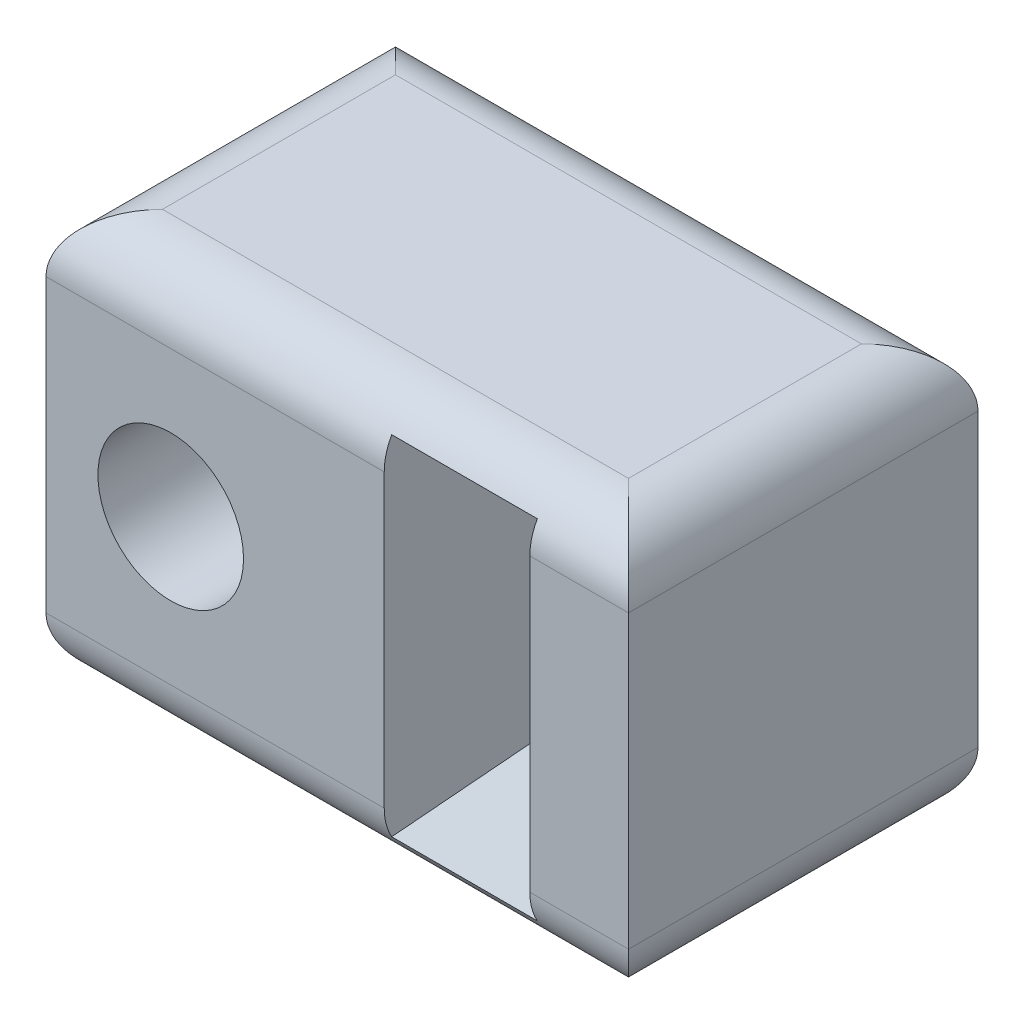
SolidWorks part; units mm, degrees
ref_plane "Front Plane" through (0, 0, 0) normal (0, 0, 1) x (1, 0, 0)
ref_plane "Top Plane" through (0, 0, 0) normal (0, 1, 0) x (1, 0, 0)
ref_plane "Right Plane" through (0, 0, 0) normal (1, 0, 0) x (0, 0, -1)
sketch "Sketch1" plane through (0, 0, 0) normal (0, 0, 1) x (1, 0, 0)
  line L0 (0, 1.9206) -> (0, -2.1822) construction
  line L2 (-5, -3.5) -> (5, -3.5)
  line L3 (-5, -3.5) -> (-5, 3.5)
  line L4 (-5, 3.5) -> (5, 3.5)
  line L5 (5, -3.5) -> (5, 3.5)
  line L6 (-5, -3.5) -> (5, 3.5) construction
  line L7 (-5, 3.5) -> (5, -3.5) construction
  point P3 (0, 0)
  dimension "D1" = 10
  dimension "D2" = 7
extrude "Boss-Extrude1" add sketch "Sketch1" along normal blind 6 contours L4 L5 L2 L3
sketch "Sketch2" plane through (0, 0, 6) normal (0, 0, 1) x (1, 0, 0)
  line L1 (0.8066, -3) -> (3.3066, -3)
  line L2 (0.8066, -3) -> (0.8066, 3)
  line L3 (0.8066, 3) -> (3.3066, 3)
  line L4 (3.3066, -3) -> (3.3066, 3)
  line L5 (0.8066, -3) -> (3.3066, 3) construction
  line L6 (0.8066, 3) -> (3.3066, -3) construction
  point P0 (2.0566, 0)
  dimension "D1" = 2.5
  dimension "D2" = 6
sketch "Sketch3" plane through (0, 0, 0) normal (0, 0, -1) x (-1, 0, 0)
  line L0 (-3.3066, -3) -> (-3.3066, 3) construction
  line L1 (-3.3066, -2.5) -> (-0.8066, -2.5)
  line L2 (-3.3066, -2.5) -> (-3.3066, 2.5)
  line L3 (-3.3066, 2.5) -> (-0.8066, 2.5)
  line L4 (-0.8066, -2.5) -> (-0.8066, 2.5)
  line L5 (-3.3066, -2.5) -> (-0.8066, 2.5) construction
  line L6 (-3.3066, 2.5) -> (-0.8066, -2.5) construction
  point P0 (-2.0566, 0)
  dimension "D1" = 5
loft "Cut-Loft2" cut profiles "Sketch3", "Sketch2"
sketch "Sketch4" plane through (0, 0, 6) normal (0, 0, 1) x (1, 0, 0)
  circle A0 centre (-2.8589, 0) radius 1.25
  dimension "D1" = 2.5
extrude "Cut-Extrude1" cut sketch "Sketch4" against normal blind 6
fillet "Fillet1" radius 1 8 edges at (0, -3.5, 0) (0, 3.5, 0) (0, 3.5, 6) (0, -3.5, 6) (-5, -3.5, 3) (-5, 3.5, 3) (5, -3.5, 3) (5, 3.5, 3)
